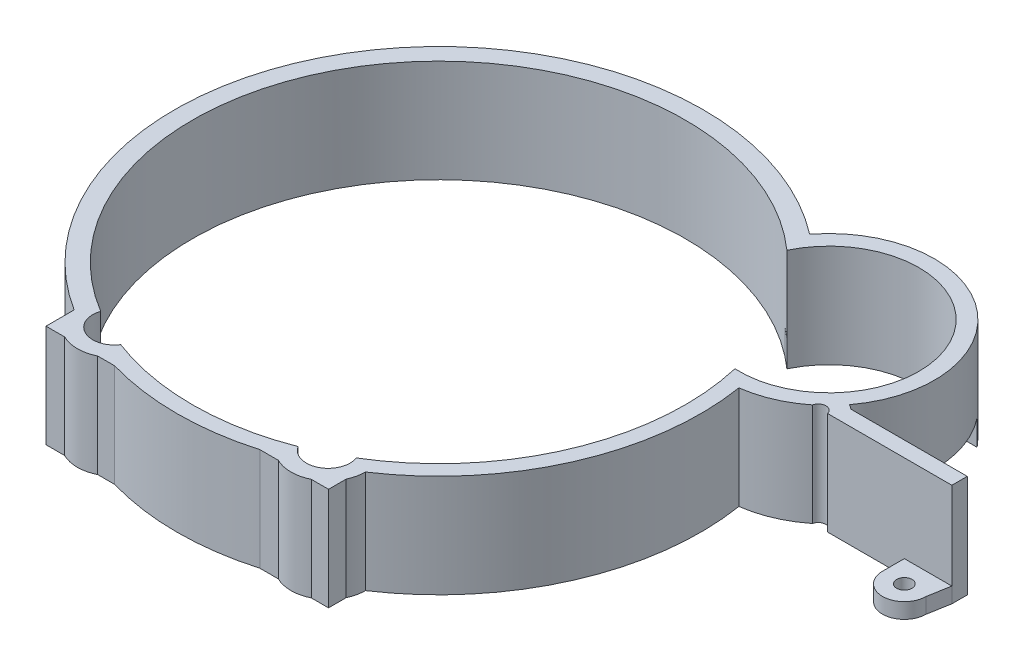
SolidWorks part; units mm, degrees
ref_plane "Alzado" through (0, 0, 0) normal (0, 0, 1) x (1, 0, 0)
ref_plane "Planta" through (0, 0, 0) normal (0, 1, 0) x (1, 0, 0)
ref_plane "Vista lateral" through (0, 0, 0) normal (1, 0, 0) x (0, 0, -1)
sketch "Croquis1" plane through (0, 0, 0) normal (0, 1, 0) x (1, 0, 0)
  circle A0 centre (0, 0) radius 48
  circle A1 centre (0, 0) radius 51
  dimension "D1" = 96
  dimension "D2" = 102
extrude "Saliente-Extruir1" add sketch "Croquis1" along normal blind 20
sketch "Croquis2" plane through (0, 20, 0) normal (0, 1, 0) x (1, 0, 0)
  line L1 (-73.7277, 57.1051) -> (-27.5, 57.1051)
  line L2 (-73.7277, 57.1051) -> (-73.7277, -57.9265)
  line L3 (-73.7277, -57.9265) -> (-27.5, -57.9265)
  line L4 (-27.5, 57.1051) -> (-27.5, -57.9265)
  dimension "D1" = 27.5
extrude "Cortar-Extruir1" cut sketch "Croquis2" against normal blind 20
sketch "Croquis3" plane through (0, 20, 0) normal (0, 1, 0) x (1, 0, 0)
  line L1 (-43.798, 61) -> (71.2336, 61)
  line L2 (-43.798, 61) -> (-43.798, 11)
  line L3 (-43.798, 11) -> (71.2336, 11)
  line L4 (71.2336, 61) -> (71.2336, 11)
  dimension "D1" = 11
  dimension "D2" = 50
extrude "Cortar-Extruir2" cut sketch "Croquis3" against normal blind 20
sketch "Croquis4" plane through (0, 20, 0) normal (0, 1, 0) x (1, 0, 0)
  circle A0 centre (47.61, 28.36) radius 17.5
  circle A1 centre (47.61, 28.36) radius 20.5
  dimension "D1" = 47.61
  dimension "D2" = 28.36
  dimension "D3" = 35
extrude "Saliente-Extruir2" add sketch "Croquis4" against normal blind 20
sketch "Croquis5" plane through (0, 20, 0) normal (0, 1, 0) x (1, 0, 0)
  line L0 (59.33, 15.36) -> (87.51, 15.36)
  line L1 (59.33, 12.36) -> (87.51, 12.36)
  line L2 (87.51, 15.36) -> (87.51, 12.36)
  line L3 (59.33, 15.36) -> (59.33, 12.36)
  arc A0 (49.8001, 10.9976) -> (46.7504, 10.8811) centre (47.61, 28.36) ccw construction
  arc A1 (50.3614, 8.0455) -> (47.3518, 7.8616) centre (47.61, 28.36) ccw construction
  dimension "D1" = 13
  dimension "D2" = 11.72
  dimension "D3" = 3
  dimension "D4" = 28.18
  dimension "D5" = 0
extrude "Saliente-Extruir3" add sketch "Croquis5" against normal blind 20
sketch "Croquis6" plane through (0, 20, 0) normal (0, 1, 0) x (1, 0, 0)
  line L0 (87.51, 15.36) -> (63.4609, 15.36) construction
  line L2 (127.998, 51.6136) -> (16.5182, 51.6136)
  line L3 (127.998, 51.6136) -> (127.998, 15.36)
  line L4 (127.998, 15.36) -> (16.5182, 15.36)
  line L5 (16.5182, 51.6136) -> (16.5182, 15.36)
  dimension "D1" = 0
extrude "Cortar-Extruir3" cut sketch "Croquis6" against normal blind 20
sketch "Croquis7" plane through (0, 20, 0) normal (0, 1, 0) x (1, 0, 0)
  circle A0 centre (0, 0) radius 48
extrude "Cortar-Extruir4" cut sketch "Croquis7" against normal blind 20
sketch "Croquis8" plane through (0, 20, 0) normal (0, 1, 0) x (1, 0, 0)
  line L0 (-27.5, -42.9506) -> (-27.5, -39.3415) construction
  circle A0 centre (-20.65, -42.5015) radius 4.25
  dimension "D1" = 6.85
  dimension "D3" = 8.5
  dimension "D2" = 3.16
extrude "Cortar-Extruir5" cut sketch "Croquis8" against normal blind 20
sketch "Croquis9" plane through (0, 20, 0) normal (0, 1, 0) x (1, 0, 0)
  circle A0 centre (-20.65, -42.5015) radius 4.25
  circle A1 centre (-20.65, -42.5015) radius 7.25
extrude "Saliente-Extruir4" add sketch "Croquis9" against normal blind 20
sketch "Croquis10" plane through (0, 20, 0) normal (0, 1, 0) x (1, 0, 0)
  line L1 (-27.5, -39.3415) -> (-30.0315, -39.3415)
  line L2 (-27.5, -39.3415) -> (-27.5, -46.6317)
  line L3 (-27.5, -46.6317) -> (-30.0315, -46.6317)
  line L4 (-30.0315, -39.3415) -> (-30.0315, -46.6317)
extrude "Cortar-Extruir6" cut sketch "Croquis10" against normal blind 20
sketch "Croquis11" plane through (0, 20, 0) normal (0, 1, 0) x (1, 0, 0)
  circle A0 centre (0, 0) radius 48
extrude "Cortar-Extruir7" cut sketch "Croquis11" against normal blind 20
sketch "Croquis12" plane through (0, 0, 0) normal (0, -1, 0) x (-1, 0, 0)
  circle A0 centre (0, 0) radius 48
  circle A1 centre (20.65, -42.5015) radius 4.25
  arc M2 (24.6848, -41.1662) -> (17.1067, -44.8482) centre (20.65, -42.5015) cw
extrude "Saliente-Extruir5" add sketch "Croquis12" against normal blind 3 contours A0 M2 region at (-21.6024, 0, 44.4616)
sketch "Croquis13" plane through (0, 3, 0) normal (0, 1, 0) x (1, 0, 0)
  circle A0 centre (-20.65, -42.5015) radius 4.25
  circle A1 centre (-20.65, -42.5015) radius 2.5
extrude "Saliente-Extruir6" add sketch "Croquis13" against normal blind 3
sketch "Croquis14" plane through (0, 3, 0) normal (0, 1, 0) x (1, 0, 0)
  circle A0 centre (-20.65, -42.5015) radius 2.5
extrude "Cortar-Extruir8" cut sketch "Croquis14" against normal blind 3
sketch "Croquis16" plane through (0, 20, 0) normal (0, 1, 0) x (1, 0, 0)
  line L0 (-20.65, -42.5015) -> (0, 0) construction
  line L1 (0, 0) -> (20.9456, -42.4988) construction
  circle A0 centre (20.9456, -42.4988) radius 4.25
  dimension "D1" = 47.38
  dimension "D3" = 8.5
  dimension "D2" = 52.15
extrude "Cortar-Extruir9" cut sketch "Croquis16" against normal blind 20
sketch "Croquis17" plane through (0, 20, 0) normal (0, 1, 0) x (1, 0, 0)
  circle A0 centre (20.9456, -42.4988) radius 4.25
  circle A1 centre (20.9456, -42.4988) radius 7.25
extrude "Saliente-Extruir7" add sketch "Croquis17" against normal blind 20
sketch "Croquis18" plane through (0, 20, 0) normal (0, 1, 0) x (1, 0, 0)
  circle A0 centre (0, 0) radius 48
extrude "Cortar-Extruir10" cut sketch "Croquis18" against normal blind 20
sketch "Croquis19" plane through (0, 0, 0) normal (0, -1, 0) x (-1, 0, 0)
  circle A0 centre (-20.9456, -42.4988) radius 4.25
  circle A1 centre (-20.9456, -42.4988) radius 2.5
extrude "Saliente-Extruir8" add sketch "Croquis19" against normal blind 3
sketch "Croquis20" plane through (0, 3, 0) normal (0, 1, 0) x (1, 0, 0)
  circle A0 centre (-20.65, -42.5015) radius 2.5
  circle A1 centre (-20.65, -42.5015) radius 4.25
extrude "Saliente-Extruir9" add sketch "Croquis20" against normal blind 3
sketch "Croquis21" plane through (0, 0, 0) normal (0, -1, 0) x (-1, 0, 0)
  line L0 (-60.426, 12.36) -> (-87.51, 12.36) construction
  line L1 (-87.51, 12.36) -> (-87.51, 15.36) construction
  circle A0 centre (-82.51, 8.11) radius 4.25
  circle A1 centre (-82.51, 8.11) radius 2.5
  dimension "D1" = 4.25
  dimension "D2" = 8.5
  dimension "D3" = 5
extrude "Saliente-Extruir10" add sketch "Croquis21" against normal blind 3 separate body
sketch "Croquis22" plane through (0, 0, 0) normal (0, -1, 0) x (-1, 0, 0)
  line L0 (-78.26, 8.11) -> (-78.26, 13.4729)
  line L1 (-78.26, 13.4729) -> (-87.51, 12.36)
  line L2 (-87.51, 12.36) -> (-86.76, 8.11)
  line L3 (-86.76, 8.11) -> (-85.01, 8.11)
  line L4 (-80.01, 8.11) -> (-78.26, 8.11)
  circle A0 centre (-82.51, 8.11) radius 2.5
  circle A1 centre (-82.51, 8.11) radius 4.25 construction
  circle M2 centre (-82.51, 8.11) radius 4.25
extrude "Saliente-Extruir11" add sketch "Croquis22" against normal blind 3 contours L1 L2 L0 M2 region at (82.51, 0, -12.4669)
sketch "Croquis24" plane through (0, 20, 0) normal (0, 1, 0) x (1, 0, 0)
  line L0 (82.51, 8.11) -> (61.8528, 11.9983) construction
  line L1 (60.426, 12.36) -> (87.51, 12.36) construction
  circle A0 centre (61.8528, 11.9983) radius 1.5
  dimension "D1" = 21.02
  dimension "D3" = 3
  dimension "D2" = 10.66
extrude "Cortar-Extruir12" cut sketch "Croquis24" against normal blind 20
sketch "Croquis25" plane through (0, 20, 0) normal (0, 1, 0) x (1, 0, 0)
  line L0 (63.3085, 12.36) -> (66.3382, 12.36)
  line L1 (63.3085, 12.36) -> (87.51, 12.36) construction
  circle A0 centre (61.8528, 11.9983) radius 1.5
  circle A1 centre (61.8528, 11.9983) radius 4.5
  circle A2 centre (47.61, 28.36) radius 20.5
  arc M1 (60.3902, 12.3314) -> (63.3085, 12.36) centre (61.8528, 11.9983) cw
  line M2 (63.3085, 12.36) -> (87.51, 12.36)
  line M4 (87.51, 15.36) -> (59.3254, 15.36)
  arc M5 (59.3254, 15.36) -> (49.8001, 10.9976) centre (47.61, 28.36) cw
  arc M18 (50.3614, 8.0455) -> (60.3902, 12.3314) centre (47.61, 28.36) ccw
  dimension "D1" = 9
extrude "Saliente-Extruir12" add sketch "Croquis25" against normal blind 20 contours A2 A1 M1 M4 M5 M18 | A2 A1 M4 M5 | A2 A1 M4 | A2 A0 A1 M2 M4 region at (64.2845, 20, -13.7368) region at (59.7043, 20, -13.4783) region at (64.1036, 20, -15.5723) region at (61.391, 20, -15.7797)
sketch "Croquis26" plane through (0, 20, 0) normal (0, 1, 0) x (1, 0, 0)
  line L1 (-27.5, -44.8763) -> (-24.6102, -44.8763)
  line L2 (-27.5, -44.8763) -> (-27.5, -49.0015)
  line L3 (-27.5, -49.0015) -> (-24.6102, -49.0015)
  line L4 (-24.6102, -44.8763) -> (-24.6102, -49.0015)
  dimension "D1" = 9.66
extrude "Saliente-Extruir16" add sketch "Croquis26" against normal blind 20
sketch "Croquis29" plane through (0, 20, 0) normal (0, 1, 0) x (1, 0, 0)
  line L1 (-24.6102, -49.0015) -> (20.1294, -49.0015)
  line L2 (-24.6102, -49.0015) -> (-24.6102, -48.1748)
  line L3 (-24.6102, -48.1748) -> (20.1294, -48.1748)
  line L4 (20.1294, -49.0015) -> (20.1294, -48.1748)
extrude "Saliente-Extruir17" add sketch "Croquis29" against normal blind 20
sketch "Croquis30" plane through (0, 20, 0) normal (0, 1, 0) x (1, 0, 0)
  line L0 (14.1371, -49.0015) -> (17.7397, -49.0015) construction
  line L1 (24.1515, -49.0015) -> (27.5097, -49.0015)
  line L2 (24.1515, -49.0015) -> (24.1515, -45.4015)
  line L3 (24.1515, -45.4015) -> (27.5097, -45.4015)
  line L4 (27.5097, -49.0015) -> (27.5097, -45.4015)
  arc A0 (17.7397, -49.0015) -> (28.1956, -42.4972) centre (20.9456, -42.4988) ccw construction
  dimension "D1" = 0
  dimension "D2" = 9.77
  dimension "D3" = 3.6
extrude "Saliente-Extruir18" add sketch "Croquis30" against normal blind 20
sketch "Croquis31" plane through (0, 20, 0) normal (0, 1, 0) x (1, 0, 0)
  circle A0 centre (47.61, 28.36) radius 17.5
  circle A1 centre (47.61, 28.36) radius 20.5
extrude "Saliente-Extruir20" add sketch "Croquis31" against normal blind 15
sketch "Croquis32" plane through (0, 20, 0) normal (0, 1, 0) x (1, 0, 0)
  line L0 (0, 0) -> (23.1137, 42.0685)
  line L1 (0, 0) -> (48, 0)
  circle A0 centre (0, 0) radius 48
  arc M1 (46.7226, 11) -> (46.7504, 10.8811) centre (0, 0) cw
  arc M2 (46.7504, 10.8811) -> (60.1664, 16.1704) centre (47.61, 28.36) cw
  arc M14 (63.9496, 15.9799) -> (47.3518, 7.8616) centre (47.61, 28.36) ccw
  arc M15 (47.3518, 7.8616) -> (24.9295, -41.0185) centre (0, 0) cw
extrude "Cortar-Extruir14" cut sketch "Croquis32" against normal blind 15 contours A0 L0 L1 M14 M15 | A0 M14 M2 | A0 M1 M2 region at (22.8113, 20, -13.4425) region at (30.4309, 20, -36.6514) region at (37.3083, 20, -22.2235)
sketch "Croquis33" plane through (0, 20, 0) normal (0, 1, 0) x (1, 0, 0)
  circle A0 centre (47.61, 28.36) radius 17.5
extrude "Cortar-Extruir16" cut sketch "Croquis33" against normal blind 30
sketch "Croquis34" plane through (0, 20, 0) normal (0, 1, 0) x (1, 0, 0)
  circle A0 centre (61.8528, 11.9983) radius 1.5
extrude "Cortar-Extruir17" cut sketch "Croquis34" against normal blind 30
sketch "Croquis35" plane through (0, 5, 0) normal (0, -1, 0) x (-1, 0, 0)
  line L5 (-31.8309, 35.9276) -> (-29.4621, 37.8944)
  line L6 (-63.5827, 41.21) -> (-59.4897, 41.21)
  arc A0 (-63.5827, 41.21) -> (-29.4621, 37.8944) centre (-47.61, 28.36) cw
  arc A1 (-29.4621, 37.8944) -> (-63.9496, 15.9799) centre (-47.61, 28.36) ccw construction
  arc A2 (-29.4621, 37.8944) -> (-31.8309, 35.9276) centre (0, 0) ccw construction
  arc A3 (-31.8309, 35.9276) -> (-59.4897, 41.21) centre (-47.61, 28.36) ccw
extrude "Saliente-Extruir21" add sketch "Croquis35" along normal blind 5
sketch "Croquis38" plane through (0, 20, 0) normal (0, 1, 0) x (1, 0, 0)
  line L0 (-27.5, -49.0015) -> (-27.5, -39.3415) construction
  line L1 (29.4621, 37.8944) -> (31.7916, 38.3176)
  line L2 (31.7916, 38.3176) -> (31.348, 40.8418)
  line L3 (-27.5, -39.3415) -> (-27.5, -43.5258)
  arc A0 (-27.5, -39.3415) -> (29.4621, 37.8944) centre (0, 0) cw
  arc A1 (63.9496, 15.9799) -> (29.4621, 37.8944) centre (47.61, 28.36) ccw construction
  arc A2 (31.348, 40.8418) -> (-27.5, -43.5258) centre (0, 0) ccw
extrude "Saliente-Extruir23" add sketch "Croquis38" against normal blind 20
sketch "Croquis39" plane through (0, 3, 0) normal (0, 1, 0) x (1, 0, 0)
  circle A0 centre (-20.65, -42.5015) radius 2.5
  circle A1 centre (-20.65, -42.5015) radius 1.5
  circle A2 centre (20.9456, -42.4988) radius 2.5
  circle A3 centre (20.9456, -42.4988) radius 1.5
  circle A4 centre (82.51, 8.11) radius 2.5
  circle A5 centre (82.51, 8.11) radius 1.5
extrude "Saliente-Extruir24" add sketch "Croquis39" against normal blind 3
